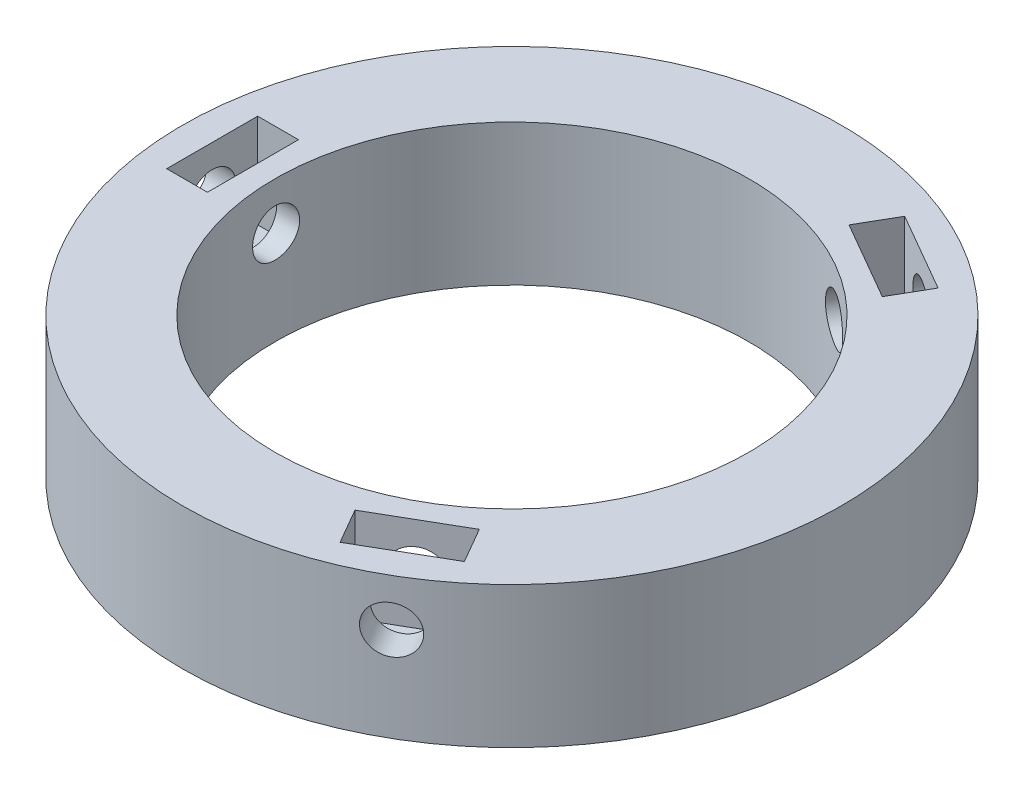
SolidWorks part; units mm, degrees
ref_plane "Front Plane" through (0, 0, 0) normal (0, 0, 1) x (1, 0, 0)
ref_plane "Top Plane" through (0, 0, 0) normal (0, 1, 0) x (1, 0, 0)
ref_plane "Right Plane" through (0, 0, 0) normal (1, 0, 0) x (0, 0, -1)
sketch "Sketch1" plane through (0, 0, 0) normal (0, 1, 0) x (1, 0, 0)
  circle A0 centre (0, 0) radius 15.1
  circle A1 centre (0, 0) radius 21
  dimension "D1" = 30.2
  dimension "D2" = 42
extrude "Boss-Extrude1" add sketch "Sketch1" along normal blind 9
sketch "Sketch2" plane through (0, 9, 0) normal (0, 1, 0) x (1, 0, 0)
  line L1 (-19.1, 2.9) -> (-16.5, 2.9)
  line L2 (-19.1, 2.9) -> (-19.1, -2.9)
  line L3 (-19.1, -2.9) -> (-16.5, -2.9)
  line L4 (-16.5, 2.9) -> (-16.5, -2.9)
  dimension "D1" = 5.8
  dimension "D2" = 2.6
  dimension "D3" = 16.5
  dimension "D4" = 2.9
extrude "Cut-Extrude1" cut sketch "Sketch2" against normal blind 6
sketch "Sketch3" plane through (-16.5, 0, 0) normal (-1, 0, 0) x (0, 0, 1)
  line L0 (21, 9) -> (-21, 9) construction
  circle A0 centre (0, 6) radius 1.5
  point P4 (0, 0)
  point P6 (-2.1827, 6)
  dimension "D2" = 3
  dimension "D1" = 3
  dimension "D3" = 0
extrude "Cut-Extrude2" cut sketch "Sketch3" against normal blind 6 and the other way blind 6
ref_axis "Axis1" through (0, 9.45, 0) along (0, -1, 0)
pattern_circular "CirPattern1" count 3 over 360 about axis through (0, 9.45, 0) along (0, -1, 0) of "Cut-Extrude1", "Cut-Extrude2"
